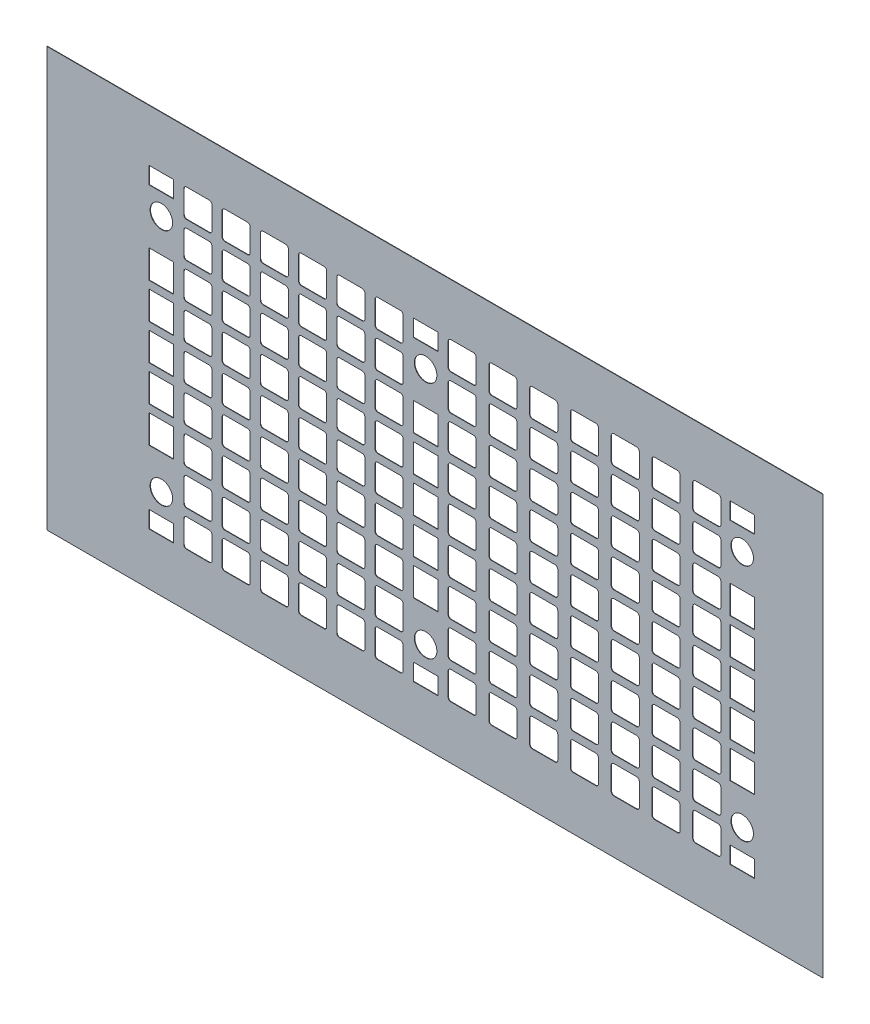
SolidWorks part; units mm, degrees
ref_plane "Спереди (XY)" through (0, 0, 0) normal (0, 0, 1) x (1, 0, 0)
ref_plane "Сверху (XZ)" through (0, 0, 0) normal (0, 1, 0) x (1, 0, 0)
ref_plane "Справа (ZY)" through (0, 0, 0) normal (1, 0, 0) x (0, 0, -1)
sketch "Эскиз1" plane through (0, 0, 0) normal (0, 0, 1) x (1, 0, 0)
  line L0 (-28, 59) -> (248, 59) construction
  line L1 (0, 0) -> (233, 0) construction
  line L2 (0, 0) -> (0, 118) construction
  line L3 (0, 118) -> (233, 118) construction
  line L4 (233, 0) -> (233, 118) construction
  line L5 (-28, -15.5) -> (248, -15.5)
  line L6 (-28, -15.5) -> (-28, 133.5)
  line L7 (-28, 133.5) -> (248, 133.5)
  line L8 (248, -15.5) -> (248, 133.5)
  line L9 (12.74, 16.55) -> (219.34, 16.55) construction
  line L10 (34.34, 114) -> (34.34, 106)
  line L11 (21.74, 115) -> (29.74, 115)
  line L12 (20.74, 114) -> (20.74, 106)
  line L13 (21.74, 105) -> (29.74, 105)
  line L14 (30.74, 114) -> (30.74, 106)
  line L15 (35.34, 115) -> (43.34, 115)
  line L16 (44.34, 114) -> (44.34, 106)
  line L17 (35.34, 105) -> (43.34, 105)
  line L18 (47.94, 114) -> (47.94, 106)
  line L19 (48.94, 115) -> (56.94, 115)
  line L20 (57.94, 114) -> (57.94, 106)
  line L21 (48.94, 105) -> (56.94, 105)
  line L22 (61.54, 114) -> (61.54, 106)
  line L23 (62.54, 115) -> (70.54, 115)
  line L24 (71.54, 114) -> (71.54, 106)
  line L25 (62.54, 105) -> (70.54, 105)
  line L26 (75.14, 114) -> (75.14, 106)
  line L27 (76.14, 115) -> (84.14, 115)
  line L28 (85.14, 114) -> (85.14, 106)
  line L29 (76.14, 105) -> (84.14, 105)
  line L30 (88.74, 114) -> (88.74, 106)
  line L31 (89.74, 115) -> (97.74, 115)
  line L32 (98.74, 114) -> (98.74, 106)
  line L33 (89.74, 105) -> (97.74, 105)
  line L34 (34.34, 101.3) -> (34.34, 93.3)
  line L35 (35.34, 102.3) -> (43.34, 102.3)
  line L36 (44.34, 101.3) -> (44.34, 93.3)
  line L37 (35.34, 92.3) -> (43.34, 92.3)
  line L38 (47.94, 101.3) -> (47.94, 93.3)
  line L39 (48.94, 102.3) -> (56.94, 102.3)
  line L40 (57.94, 101.3) -> (57.94, 93.3)
  line L41 (48.94, 92.3) -> (56.94, 92.3)
  line L42 (61.54, 101.3) -> (61.54, 93.3)
  line L43 (62.54, 102.3) -> (70.54, 102.3)
  line L44 (71.54, 101.3) -> (71.54, 93.3)
  line L45 (62.54, 92.3) -> (70.54, 92.3)
  line L46 (75.14, 101.3) -> (75.14, 93.3)
  line L47 (76.14, 102.3) -> (84.14, 102.3)
  line L48 (85.14, 101.3) -> (85.14, 93.3)
  line L49 (76.14, 92.3) -> (84.14, 92.3)
  line L50 (88.74, 101.3) -> (88.74, 93.3)
  line L51 (89.74, 102.3) -> (97.74, 102.3)
  line L52 (98.74, 101.3) -> (98.74, 93.3)
  line L53 (89.74, 92.3) -> (97.74, 92.3)
  line L54 (34.34, 88.6) -> (34.34, 80.6)
  line L55 (35.34, 89.6) -> (43.34, 89.6)
  line L56 (44.34, 88.6) -> (44.34, 80.6)
  line L57 (35.34, 79.6) -> (43.34, 79.6)
  line L58 (47.94, 88.6) -> (47.94, 80.6)
  line L59 (48.94, 89.6) -> (56.94, 89.6)
  line L60 (57.94, 88.6) -> (57.94, 80.6)
  line L61 (48.94, 79.6) -> (56.94, 79.6)
  line L62 (61.54, 88.6) -> (61.54, 80.6)
  line L63 (62.54, 89.6) -> (70.54, 89.6)
  line L64 (71.54, 88.6) -> (71.54, 80.6)
  line L65 (62.54, 79.6) -> (70.54, 79.6)
  line L66 (75.14, 88.6) -> (75.14, 80.6)
  line L67 (76.14, 89.6) -> (84.14, 89.6)
  line L68 (85.14, 88.6) -> (85.14, 80.6)
  line L69 (76.14, 79.6) -> (84.14, 79.6)
  line L70 (88.74, 88.6) -> (88.74, 80.6)
  line L71 (89.74, 89.6) -> (97.74, 89.6)
  line L72 (98.74, 88.6) -> (98.74, 80.6)
  line L73 (89.74, 79.6) -> (97.74, 79.6)
  line L74 (34.34, 75.9) -> (34.34, 67.9)
  line L75 (35.34, 76.9) -> (43.34, 76.9)
  line L76 (44.34, 75.9) -> (44.34, 67.9)
  line L77 (35.34, 66.9) -> (43.34, 66.9)
  line L78 (47.94, 75.9) -> (47.94, 67.9)
  line L79 (48.94, 76.9) -> (56.94, 76.9)
  line L80 (57.94, 75.9) -> (57.94, 67.9)
  line L81 (48.94, 66.9) -> (56.94, 66.9)
  line L82 (61.54, 75.9) -> (61.54, 67.9)
  line L83 (62.54, 76.9) -> (70.54, 76.9)
  line L84 (71.54, 75.9) -> (71.54, 67.9)
  line L85 (62.54, 66.9) -> (70.54, 66.9)
  line L86 (75.14, 75.9) -> (75.14, 67.9)
  line L87 (76.14, 76.9) -> (84.14, 76.9)
  line L88 (85.14, 75.9) -> (85.14, 67.9)
  line L89 (76.14, 66.9) -> (84.14, 66.9)
  line L90 (88.74, 75.9) -> (88.74, 67.9)
  line L91 (89.74, 76.9) -> (97.74, 76.9)
  line L92 (98.74, 75.9) -> (98.74, 67.9)
  line L93 (89.74, 66.9) -> (97.74, 66.9)
  line L94 (34.34, 63.2) -> (34.34, 55.2)
  line L95 (35.34, 64.2) -> (43.34, 64.2)
  line L96 (44.34, 63.2) -> (44.34, 55.2)
  line L97 (35.34, 54.2) -> (43.34, 54.2)
  line L98 (47.94, 63.2) -> (47.94, 55.2)
  line L99 (48.94, 64.2) -> (56.94, 64.2)
  line L100 (57.94, 63.2) -> (57.94, 55.2)
  line L101 (48.94, 54.2) -> (56.94, 54.2)
  line L102 (61.54, 63.2) -> (61.54, 55.2)
  line L103 (62.54, 64.2) -> (70.54, 64.2)
  line L104 (71.54, 63.2) -> (71.54, 55.2)
  line L105 (62.54, 54.2) -> (70.54, 54.2)
  line L106 (75.14, 63.2) -> (75.14, 55.2)
  line L107 (76.14, 64.2) -> (84.14, 64.2)
  line L108 (85.14, 63.2) -> (85.14, 55.2)
  line L109 (76.14, 54.2) -> (84.14, 54.2)
  line L110 (88.74, 63.2) -> (88.74, 55.2)
  line L111 (89.74, 64.2) -> (97.74, 64.2)
  line L112 (98.74, 63.2) -> (98.74, 55.2)
  line L113 (89.74, 54.2) -> (97.74, 54.2)
  line L114 (34.34, 50.5) -> (34.34, 42.5)
  line L115 (35.34, 51.5) -> (43.34, 51.5)
  line L116 (44.34, 50.5) -> (44.34, 42.5)
  line L117 (35.34, 41.5) -> (43.34, 41.5)
  line L118 (47.94, 50.5) -> (47.94, 42.5)
  line L119 (48.94, 51.5) -> (56.94, 51.5)
  line L120 (57.94, 50.5) -> (57.94, 42.5)
  line L121 (48.94, 41.5) -> (56.94, 41.5)
  line L122 (61.54, 50.5) -> (61.54, 42.5)
  line L123 (62.54, 51.5) -> (70.54, 51.5)
  line L124 (71.54, 50.5) -> (71.54, 42.5)
  line L125 (62.54, 41.5) -> (70.54, 41.5)
  line L126 (75.14, 50.5) -> (75.14, 42.5)
  line L127 (76.14, 51.5) -> (84.14, 51.5)
  line L128 (85.14, 50.5) -> (85.14, 42.5)
  line L129 (76.14, 41.5) -> (84.14, 41.5)
  line L130 (88.74, 50.5) -> (88.74, 42.5)
  line L131 (89.74, 51.5) -> (97.74, 51.5)
  line L132 (98.74, 50.5) -> (98.74, 42.5)
  line L133 (89.74, 41.5) -> (97.74, 41.5)
  line L134 (34.34, 37.8) -> (34.34, 29.8)
  line L135 (35.34, 38.8) -> (43.34, 38.8)
  line L136 (44.34, 37.8) -> (44.34, 29.8)
  line L137 (35.34, 28.8) -> (43.34, 28.8)
  line L138 (47.94, 37.8) -> (47.94, 29.8)
  line L139 (48.94, 38.8) -> (56.94, 38.8)
  line L140 (57.94, 37.8) -> (57.94, 29.8)
  line L141 (48.94, 28.8) -> (56.94, 28.8)
  line L142 (61.54, 37.8) -> (61.54, 29.8)
  line L143 (62.54, 38.8) -> (70.54, 38.8)
  line L144 (71.54, 37.8) -> (71.54, 29.8)
  line L145 (62.54, 28.8) -> (70.54, 28.8)
  line L146 (75.14, 37.8) -> (75.14, 29.8)
  line L147 (76.14, 38.8) -> (84.14, 38.8)
  line L148 (85.14, 37.8) -> (85.14, 29.8)
  line L149 (76.14, 28.8) -> (84.14, 28.8)
  line L150 (88.74, 37.8) -> (88.74, 29.8)
  line L151 (89.74, 38.8) -> (97.74, 38.8)
  line L152 (98.74, 37.8) -> (98.74, 29.8)
  line L153 (89.74, 28.8) -> (97.74, 28.8)
  line L154 (34.34, 25.1) -> (34.34, 17.1)
  line L155 (35.34, 26.1) -> (43.34, 26.1)
  line L156 (44.34, 25.1) -> (44.34, 17.1)
  line L157 (35.34, 16.1) -> (43.34, 16.1)
  line L158 (47.94, 25.1) -> (47.94, 17.1)
  line L159 (48.94, 26.1) -> (56.94, 26.1)
  line L160 (57.94, 25.1) -> (57.94, 17.1)
  line L161 (48.94, 16.1) -> (56.94, 16.1)
  line L162 (61.54, 25.1) -> (61.54, 17.1)
  line L163 (62.54, 26.1) -> (70.54, 26.1)
  line L164 (71.54, 25.1) -> (71.54, 17.1)
  line L165 (62.54, 16.1) -> (70.54, 16.1)
  line L166 (75.14, 25.1) -> (75.14, 17.1)
  line L167 (76.14, 26.1) -> (84.14, 26.1)
  line L168 (85.14, 25.1) -> (85.14, 17.1)
  line L169 (76.14, 16.1) -> (84.14, 16.1)
  line L170 (88.74, 25.1) -> (88.74, 17.1)
  line L171 (89.74, 26.1) -> (97.74, 26.1)
  line L172 (98.74, 25.1) -> (98.74, 17.1)
  line L173 (89.74, 16.1) -> (97.74, 16.1)
  line L174 (34.34, 12.4) -> (34.34, 4.4)
  line L175 (35.34, 13.4) -> (43.34, 13.4)
  line L176 (44.34, 12.4) -> (44.34, 4.4)
  line L177 (35.34, 3.4) -> (43.34, 3.4)
  line L178 (47.94, 12.4) -> (47.94, 4.4)
  line L179 (48.94, 13.4) -> (56.94, 13.4)
  line L180 (57.94, 12.4) -> (57.94, 4.4)
  line L181 (48.94, 3.4) -> (56.94, 3.4)
  line L182 (61.54, 12.4) -> (61.54, 4.4)
  line L183 (62.54, 13.4) -> (70.54, 13.4)
  line L184 (71.54, 12.4) -> (71.54, 4.4)
  line L185 (62.54, 3.4) -> (70.54, 3.4)
  line L186 (75.14, 12.4) -> (75.14, 4.4)
  line L187 (76.14, 13.4) -> (84.14, 13.4)
  line L188 (85.14, 12.4) -> (85.14, 4.4)
  line L189 (76.14, 3.4) -> (84.14, 3.4)
  line L190 (88.74, 12.4) -> (88.74, 4.4)
  line L191 (89.74, 13.4) -> (97.74, 13.4)
  line L192 (98.74, 12.4) -> (98.74, 4.4)
  line L193 (89.74, 3.4) -> (97.74, 3.4)
  line L194 (20.74, 101.3) -> (20.74, 93.3)
  line L195 (21.74, 102.3) -> (29.74, 102.3)
  line L196 (30.74, 101.3) -> (30.74, 93.3)
  line L197 (21.74, 92.3) -> (29.74, 92.3)
  line L198 (20.74, 88.6) -> (20.74, 80.6)
  line L199 (21.74, 89.6) -> (29.74, 89.6)
  line L200 (30.74, 88.6) -> (30.74, 80.6)
  line L201 (21.74, 79.6) -> (29.74, 79.6)
  line L202 (20.74, 75.9) -> (20.74, 67.9)
  line L203 (21.74, 76.9) -> (29.74, 76.9)
  line L204 (30.74, 75.9) -> (30.74, 67.9)
  line L205 (21.74, 66.9) -> (29.74, 66.9)
  line L206 (20.74, 63.2) -> (20.74, 55.2)
  line L207 (21.74, 64.2) -> (29.74, 64.2)
  line L208 (30.74, 63.2) -> (30.74, 55.2)
  line L209 (21.74, 54.2) -> (29.74, 54.2)
  line L210 (20.74, 50.5) -> (20.74, 42.5)
  line L211 (21.74, 51.5) -> (29.74, 51.5)
  line L212 (30.74, 50.5) -> (30.74, 42.5)
  line L213 (21.74, 41.5) -> (29.74, 41.5)
  line L214 (20.74, 37.8) -> (20.74, 29.8)
  line L215 (21.74, 38.8) -> (29.74, 38.8)
  line L216 (30.74, 37.8) -> (30.74, 29.8)
  line L217 (21.74, 28.8) -> (29.74, 28.8)
  line L218 (20.74, 25.1) -> (20.74, 17.1)
  line L219 (21.74, 26.1) -> (29.74, 26.1)
  line L220 (30.74, 25.1) -> (30.74, 17.1)
  line L221 (21.74, 16.1) -> (29.74, 16.1)
  line L222 (20.74, 12.4) -> (20.74, 4.4)
  line L223 (21.74, 13.4) -> (29.74, 13.4)
  line L224 (30.74, 12.4) -> (30.74, 4.4)
  line L225 (21.74, 3.4) -> (29.74, 3.4)
  line L226 (106.74, 16.55) -> (106.74, 101.45) construction
  line L227 (123.74, 115) -> (115.74, 115)
  line L228 (114.74, 114) -> (114.74, 106)
  line L229 (123.74, 105) -> (115.74, 105)
  line L230 (124.74, 114) -> (124.74, 106)
  line L231 (139.24, 114) -> (139.24, 106)
  line L232 (138.24, 105) -> (130.24, 105)
  line L233 (129.24, 114) -> (129.24, 106)
  line L234 (138.24, 115) -> (130.24, 115)
  line L235 (153.74, 114) -> (153.74, 106)
  line L236 (152.74, 105) -> (144.74, 105)
  line L237 (143.74, 114) -> (143.74, 106)
  line L238 (152.74, 115) -> (144.74, 115)
  line L239 (168.24, 114) -> (168.24, 106)
  line L240 (167.24, 105) -> (159.24, 105)
  line L241 (158.24, 114) -> (158.24, 106)
  line L242 (167.24, 115) -> (159.24, 115)
  line L243 (182.74, 114) -> (182.74, 106)
  line L244 (181.74, 105) -> (173.74, 105)
  line L245 (172.74, 114) -> (172.74, 106)
  line L246 (181.74, 115) -> (173.74, 115)
  line L247 (197.24, 114) -> (197.24, 106)
  line L248 (196.24, 105) -> (188.24, 105)
  line L249 (187.24, 114) -> (187.24, 106)
  line L250 (196.24, 115) -> (188.24, 115)
  line L251 (211.74, 114) -> (211.74, 106)
  line L252 (210.74, 105) -> (202.74, 105)
  line L253 (201.74, 114) -> (201.74, 106)
  line L254 (210.74, 115) -> (202.74, 115)
  line L255 (139.24, 101.3) -> (139.24, 93.3)
  line L256 (138.24, 92.3) -> (130.24, 92.3)
  line L257 (129.24, 101.3) -> (129.24, 93.3)
  line L258 (138.24, 102.3) -> (130.24, 102.3)
  line L259 (153.74, 101.3) -> (153.74, 93.3)
  line L260 (152.74, 92.3) -> (144.74, 92.3)
  line L261 (143.74, 101.3) -> (143.74, 93.3)
  line L262 (152.74, 102.3) -> (144.74, 102.3)
  line L263 (168.24, 101.3) -> (168.24, 93.3)
  line L264 (167.24, 92.3) -> (159.24, 92.3)
  line L265 (158.24, 101.3) -> (158.24, 93.3)
  line L266 (167.24, 102.3) -> (159.24, 102.3)
  line L267 (182.74, 101.3) -> (182.74, 93.3)
  line L268 (181.74, 92.3) -> (173.74, 92.3)
  line L269 (172.74, 101.3) -> (172.74, 93.3)
  line L270 (181.74, 102.3) -> (173.74, 102.3)
  line L271 (197.24, 101.3) -> (197.24, 93.3)
  line L272 (196.24, 92.3) -> (188.24, 92.3)
  line L273 (187.24, 101.3) -> (187.24, 93.3)
  line L274 (196.24, 102.3) -> (188.24, 102.3)
  line L275 (211.74, 101.3) -> (211.74, 93.3)
  line L276 (210.74, 92.3) -> (202.74, 92.3)
  line L277 (201.74, 101.3) -> (201.74, 93.3)
  line L278 (210.74, 102.3) -> (202.74, 102.3)
  line L279 (139.24, 88.6) -> (139.24, 80.6)
  line L280 (138.24, 79.6) -> (130.24, 79.6)
  line L281 (129.24, 88.6) -> (129.24, 80.6)
  line L282 (138.24, 89.6) -> (130.24, 89.6)
  line L283 (153.74, 88.6) -> (153.74, 80.6)
  line L284 (152.74, 79.6) -> (144.74, 79.6)
  line L285 (143.74, 88.6) -> (143.74, 80.6)
  line L286 (152.74, 89.6) -> (144.74, 89.6)
  line L287 (168.24, 88.6) -> (168.24, 80.6)
  line L288 (167.24, 79.6) -> (159.24, 79.6)
  line L289 (158.24, 88.6) -> (158.24, 80.6)
  line L290 (167.24, 89.6) -> (159.24, 89.6)
  line L291 (182.74, 88.6) -> (182.74, 80.6)
  line L292 (181.74, 79.6) -> (173.74, 79.6)
  line L293 (172.74, 88.6) -> (172.74, 80.6)
  line L294 (181.74, 89.6) -> (173.74, 89.6)
  line L295 (197.24, 88.6) -> (197.24, 80.6)
  line L296 (196.24, 79.6) -> (188.24, 79.6)
  line L297 (187.24, 88.6) -> (187.24, 80.6)
  line L298 (196.24, 89.6) -> (188.24, 89.6)
  line L299 (211.74, 88.6) -> (211.74, 80.6)
  line L300 (210.74, 79.6) -> (202.74, 79.6)
  line L301 (201.74, 88.6) -> (201.74, 80.6)
  line L302 (210.74, 89.6) -> (202.74, 89.6)
  line L303 (139.24, 75.9) -> (139.24, 67.9)
  line L304 (138.24, 66.9) -> (130.24, 66.9)
  line L305 (129.24, 75.9) -> (129.24, 67.9)
  line L306 (138.24, 76.9) -> (130.24, 76.9)
  line L307 (153.74, 75.9) -> (153.74, 67.9)
  line L308 (152.74, 66.9) -> (144.74, 66.9)
  line L309 (143.74, 75.9) -> (143.74, 67.9)
  line L310 (152.74, 76.9) -> (144.74, 76.9)
  line L311 (168.24, 75.9) -> (168.24, 67.9)
  line L312 (167.24, 66.9) -> (159.24, 66.9)
  line L313 (158.24, 75.9) -> (158.24, 67.9)
  line L314 (167.24, 76.9) -> (159.24, 76.9)
  line L315 (182.74, 75.9) -> (182.74, 67.9)
  line L316 (181.74, 66.9) -> (173.74, 66.9)
  line L317 (172.74, 75.9) -> (172.74, 67.9)
  line L318 (181.74, 76.9) -> (173.74, 76.9)
  line L319 (197.24, 75.9) -> (197.24, 67.9)
  line L320 (196.24, 66.9) -> (188.24, 66.9)
  line L321 (187.24, 75.9) -> (187.24, 67.9)
  line L322 (196.24, 76.9) -> (188.24, 76.9)
  line L323 (211.74, 75.9) -> (211.74, 67.9)
  line L324 (210.74, 66.9) -> (202.74, 66.9)
  line L325 (201.74, 75.9) -> (201.74, 67.9)
  line L326 (210.74, 76.9) -> (202.74, 76.9)
  line L327 (139.24, 63.2) -> (139.24, 55.2)
  line L328 (138.24, 54.2) -> (130.24, 54.2)
  line L329 (129.24, 63.2) -> (129.24, 55.2)
  line L330 (138.24, 64.2) -> (130.24, 64.2)
  line L331 (153.74, 63.2) -> (153.74, 55.2)
  line L332 (152.74, 54.2) -> (144.74, 54.2)
  line L333 (143.74, 63.2) -> (143.74, 55.2)
  line L334 (152.74, 64.2) -> (144.74, 64.2)
  line L335 (168.24, 63.2) -> (168.24, 55.2)
  line L336 (167.24, 54.2) -> (159.24, 54.2)
  line L337 (158.24, 63.2) -> (158.24, 55.2)
  line L338 (167.24, 64.2) -> (159.24, 64.2)
  line L339 (182.74, 63.2) -> (182.74, 55.2)
  line L340 (181.74, 54.2) -> (173.74, 54.2)
  line L341 (172.74, 63.2) -> (172.74, 55.2)
  line L342 (181.74, 64.2) -> (173.74, 64.2)
  line L343 (197.24, 63.2) -> (197.24, 55.2)
  line L344 (196.24, 54.2) -> (188.24, 54.2)
  line L345 (187.24, 63.2) -> (187.24, 55.2)
  line L346 (196.24, 64.2) -> (188.24, 64.2)
  line L347 (211.74, 63.2) -> (211.74, 55.2)
  line L348 (210.74, 54.2) -> (202.74, 54.2)
  line L349 (201.74, 63.2) -> (201.74, 55.2)
  line L350 (210.74, 64.2) -> (202.74, 64.2)
  line L351 (139.24, 50.5) -> (139.24, 42.5)
  line L352 (138.24, 41.5) -> (130.24, 41.5)
  line L353 (129.24, 50.5) -> (129.24, 42.5)
  line L354 (138.24, 51.5) -> (130.24, 51.5)
  line L355 (153.74, 50.5) -> (153.74, 42.5)
  line L356 (152.74, 41.5) -> (144.74, 41.5)
  line L357 (143.74, 50.5) -> (143.74, 42.5)
  line L358 (152.74, 51.5) -> (144.74, 51.5)
  line L359 (168.24, 50.5) -> (168.24, 42.5)
  line L360 (167.24, 41.5) -> (159.24, 41.5)
  line L361 (158.24, 50.5) -> (158.24, 42.5)
  line L362 (167.24, 51.5) -> (159.24, 51.5)
  line L363 (182.74, 50.5) -> (182.74, 42.5)
  line L364 (181.74, 41.5) -> (173.74, 41.5)
  line L365 (172.74, 50.5) -> (172.74, 42.5)
  line L366 (181.74, 51.5) -> (173.74, 51.5)
  line L367 (197.24, 50.5) -> (197.24, 42.5)
  line L368 (196.24, 41.5) -> (188.24, 41.5)
  line L369 (187.24, 50.5) -> (187.24, 42.5)
  line L370 (196.24, 51.5) -> (188.24, 51.5)
  line L371 (211.74, 50.5) -> (211.74, 42.5)
  line L372 (210.74, 41.5) -> (202.74, 41.5)
  line L373 (201.74, 50.5) -> (201.74, 42.5)
  line L374 (210.74, 51.5) -> (202.74, 51.5)
  line L375 (139.24, 37.8) -> (139.24, 29.8)
  line L376 (138.24, 28.8) -> (130.24, 28.8)
  line L377 (129.24, 37.8) -> (129.24, 29.8)
  line L378 (138.24, 38.8) -> (130.24, 38.8)
  line L379 (153.74, 37.8) -> (153.74, 29.8)
  line L380 (152.74, 28.8) -> (144.74, 28.8)
  line L381 (143.74, 37.8) -> (143.74, 29.8)
  line L382 (152.74, 38.8) -> (144.74, 38.8)
  line L383 (168.24, 37.8) -> (168.24, 29.8)
  line L384 (167.24, 28.8) -> (159.24, 28.8)
  line L385 (158.24, 37.8) -> (158.24, 29.8)
  line L386 (167.24, 38.8) -> (159.24, 38.8)
  line L387 (182.74, 37.8) -> (182.74, 29.8)
  line L388 (181.74, 28.8) -> (173.74, 28.8)
  line L389 (172.74, 37.8) -> (172.74, 29.8)
  line L390 (181.74, 38.8) -> (173.74, 38.8)
  line L391 (197.24, 37.8) -> (197.24, 29.8)
  line L392 (196.24, 28.8) -> (188.24, 28.8)
  line L393 (187.24, 37.8) -> (187.24, 29.8)
  line L394 (196.24, 38.8) -> (188.24, 38.8)
  line L395 (211.74, 37.8) -> (211.74, 29.8)
  line L396 (210.74, 28.8) -> (202.74, 28.8)
  line L397 (201.74, 37.8) -> (201.74, 29.8)
  line L398 (210.74, 38.8) -> (202.74, 38.8)
  line L399 (139.24, 25.1) -> (139.24, 17.1)
  line L400 (138.24, 16.1) -> (130.24, 16.1)
  line L401 (129.24, 25.1) -> (129.24, 17.1)
  line L402 (138.24, 26.1) -> (130.24, 26.1)
  line L403 (153.74, 25.1) -> (153.74, 17.1)
  line L404 (152.74, 16.1) -> (144.74, 16.1)
  line L405 (143.74, 25.1) -> (143.74, 17.1)
  line L406 (152.74, 26.1) -> (144.74, 26.1)
  line L407 (168.24, 25.1) -> (168.24, 17.1)
  line L408 (167.24, 16.1) -> (159.24, 16.1)
  line L409 (158.24, 25.1) -> (158.24, 17.1)
  line L410 (167.24, 26.1) -> (159.24, 26.1)
  line L411 (182.74, 25.1) -> (182.74, 17.1)
  line L412 (181.74, 16.1) -> (173.74, 16.1)
  line L413 (172.74, 25.1) -> (172.74, 17.1)
  line L414 (181.74, 26.1) -> (173.74, 26.1)
  line L415 (197.24, 25.1) -> (197.24, 17.1)
  line L416 (196.24, 16.1) -> (188.24, 16.1)
  line L417 (187.24, 25.1) -> (187.24, 17.1)
  line L418 (196.24, 26.1) -> (188.24, 26.1)
  line L419 (211.74, 25.1) -> (211.74, 17.1)
  line L420 (210.74, 16.1) -> (202.74, 16.1)
  line L421 (201.74, 25.1) -> (201.74, 17.1)
  line L422 (210.74, 26.1) -> (202.74, 26.1)
  line L423 (139.24, 12.4) -> (139.24, 4.4)
  line L424 (138.24, 3.4) -> (130.24, 3.4)
  line L425 (129.24, 12.4) -> (129.24, 4.4)
  line L426 (138.24, 13.4) -> (130.24, 13.4)
  line L427 (153.74, 12.4) -> (153.74, 4.4)
  line L428 (152.74, 3.4) -> (144.74, 3.4)
  line L429 (143.74, 12.4) -> (143.74, 4.4)
  line L430 (152.74, 13.4) -> (144.74, 13.4)
  line L431 (168.24, 12.4) -> (168.24, 4.4)
  line L432 (167.24, 3.4) -> (159.24, 3.4)
  line L433 (158.24, 12.4) -> (158.24, 4.4)
  line L434 (167.24, 13.4) -> (159.24, 13.4)
  line L435 (182.74, 12.4) -> (182.74, 4.4)
  line L436 (181.74, 3.4) -> (173.74, 3.4)
  line L437 (172.74, 12.4) -> (172.74, 4.4)
  line L438 (181.74, 13.4) -> (173.74, 13.4)
  line L439 (197.24, 12.4) -> (197.24, 4.4)
  line L440 (196.24, 3.4) -> (188.24, 3.4)
  line L441 (187.24, 12.4) -> (187.24, 4.4)
  line L442 (196.24, 13.4) -> (188.24, 13.4)
  line L443 (211.74, 12.4) -> (211.74, 4.4)
  line L444 (210.74, 3.4) -> (202.74, 3.4)
  line L445 (201.74, 12.4) -> (201.74, 4.4)
  line L446 (210.74, 13.4) -> (202.74, 13.4)
  line L447 (124.74, 101.3) -> (124.74, 93.3)
  line L448 (123.74, 92.3) -> (115.74, 92.3)
  line L449 (114.74, 101.3) -> (114.74, 93.3)
  line L450 (123.74, 102.3) -> (115.74, 102.3)
  line L451 (124.74, 88.6) -> (124.74, 80.6)
  line L452 (123.74, 79.6) -> (115.74, 79.6)
  line L453 (114.74, 88.6) -> (114.74, 80.6)
  line L454 (123.74, 89.6) -> (115.74, 89.6)
  line L455 (124.74, 75.9) -> (124.74, 67.9)
  line L456 (123.74, 66.9) -> (115.74, 66.9)
  line L457 (114.74, 75.9) -> (114.74, 67.9)
  line L458 (123.74, 76.9) -> (115.74, 76.9)
  line L459 (124.74, 63.2) -> (124.74, 55.2)
  line L460 (123.74, 54.2) -> (115.74, 54.2)
  line L461 (114.74, 63.2) -> (114.74, 55.2)
  line L462 (123.74, 64.2) -> (115.74, 64.2)
  line L463 (124.74, 50.5) -> (124.74, 42.5)
  line L464 (123.74, 41.5) -> (115.74, 41.5)
  line L465 (114.74, 50.5) -> (114.74, 42.5)
  line L466 (123.74, 51.5) -> (115.74, 51.5)
  line L467 (124.74, 37.8) -> (124.74, 29.8)
  line L468 (123.74, 28.8) -> (115.74, 28.8)
  line L469 (114.74, 37.8) -> (114.74, 29.8)
  line L470 (123.74, 38.8) -> (115.74, 38.8)
  line L471 (124.74, 25.1) -> (124.74, 17.1)
  line L472 (123.74, 16.1) -> (115.74, 16.1)
  line L473 (114.74, 25.1) -> (114.74, 17.1)
  line L474 (123.74, 26.1) -> (115.74, 26.1)
  line L475 (124.74, 12.4) -> (124.74, 4.4)
  line L476 (123.74, 3.4) -> (115.74, 3.4)
  line L477 (114.74, 12.4) -> (114.74, 4.4)
  line L478 (123.74, 13.4) -> (115.74, 13.4)
  line L483 (102.34, 76.9) -> (102.34, 66.9)
  line L484 (102.34, 89.6) -> (111.14, 89.6)
  line L485 (102.34, 89.6) -> (102.34, 79.6)
  line L486 (102.34, 79.6) -> (111.14, 79.6)
  line L487 (111.14, 89.6) -> (111.14, 79.6)
  line L488 (102.34, 76.9) -> (111.14, 76.9)
  line L489 (111.14, 76.9) -> (111.14, 66.9)
  line L490 (102.34, 66.9) -> (111.14, 66.9)
  line L491 (102.34, 64.2) -> (102.34, 54.2)
  line L492 (102.34, 64.2) -> (111.14, 64.2)
  line L493 (111.14, 64.2) -> (111.14, 54.2)
  line L494 (102.34, 54.2) -> (111.14, 54.2)
  line L495 (102.34, 51.5) -> (102.34, 41.5)
  line L496 (102.34, 51.5) -> (111.14, 51.5)
  line L497 (111.14, 51.5) -> (111.14, 41.5)
  line L498 (102.34, 41.5) -> (111.14, 41.5)
  line L499 (102.34, 38.8) -> (102.34, 28.8)
  line L500 (102.34, 38.8) -> (111.14, 38.8)
  line L501 (111.14, 38.8) -> (111.14, 28.8)
  line L502 (102.34, 28.8) -> (111.14, 28.8)
  line L503 (106.74, 101.45) -> (219.34, 101.45) construction
  line L504 (106.74, 101.45) -> (12.74, 101.45) construction
  line L505 (163.04, 101.45) -> (163.04, 0) construction
  line L506 (59.74, 101.45) -> (59.74, 0) construction
  line L507 (102.34, 9) -> (111.14, 9)
  line L508 (102.34, 115) -> (111.14, 115)
  line L509 (102.34, 115) -> (102.34, 109)
  line L510 (102.34, 109) -> (111.14, 109)
  line L511 (111.14, 115) -> (111.14, 109)
  line L512 (111.14, 3) -> (111.14, 9)
  line L513 (102.34, 3) -> (111.14, 3)
  line L514 (102.34, 3) -> (102.34, 9)
  line L515 (223.74, 3) -> (223.74, 9)
  line L516 (223.74, 3) -> (214.94, 3)
  line L517 (214.94, 3) -> (214.94, 9)
  line L518 (223.74, 9) -> (214.94, 9)
  line L519 (223.74, 38.8) -> (214.94, 38.8)
  line L520 (223.74, 51.5) -> (214.94, 51.5)
  line L521 (214.94, 51.5) -> (214.94, 41.5)
  line L522 (223.74, 41.5) -> (214.94, 41.5)
  line L523 (223.74, 51.5) -> (223.74, 41.5)
  line L524 (223.74, 64.2) -> (214.94, 64.2)
  line L525 (214.94, 64.2) -> (214.94, 54.2)
  line L526 (223.74, 54.2) -> (214.94, 54.2)
  line L527 (223.74, 64.2) -> (223.74, 54.2)
  line L528 (223.74, 76.9) -> (214.94, 76.9)
  line L529 (214.94, 76.9) -> (214.94, 66.9)
  line L530 (223.74, 66.9) -> (214.94, 66.9)
  line L531 (223.74, 76.9) -> (223.74, 66.9)
  line L532 (223.74, 79.6) -> (214.94, 79.6)
  line L533 (214.94, 89.6) -> (214.94, 79.6)
  line L534 (223.74, 89.6) -> (214.94, 89.6)
  line L535 (223.74, 89.6) -> (223.74, 79.6)
  line L536 (223.74, 109) -> (214.94, 109)
  line L537 (214.94, 115) -> (214.94, 109)
  line L538 (223.74, 115) -> (214.94, 115)
  line L539 (223.74, 115) -> (223.74, 109)
  line L540 (17.14, 51.5) -> (8.34, 51.5)
  line L541 (8.34, 51.5) -> (8.34, 41.5)
  line L542 (17.14, 41.5) -> (8.34, 41.5)
  line L543 (17.14, 51.5) -> (17.14, 41.5)
  line L544 (17.14, 3) -> (17.14, 9)
  line L545 (17.14, 3) -> (8.34, 3)
  line L546 (8.34, 3) -> (8.34, 9)
  line L547 (17.14, 9) -> (8.34, 9)
  line L548 (17.14, 38.8) -> (8.34, 38.8)
  line L549 (8.34, 38.8) -> (8.34, 28.8)
  line L550 (17.14, 28.8) -> (8.34, 28.8)
  line L551 (17.14, 38.8) -> (17.14, 28.8)
  line L552 (17.14, 64.2) -> (8.34, 64.2)
  line L553 (8.34, 64.2) -> (8.34, 54.2)
  line L554 (17.14, 54.2) -> (8.34, 54.2)
  line L555 (17.14, 64.2) -> (17.14, 54.2)
  line L556 (17.14, 76.9) -> (8.34, 76.9)
  line L557 (8.34, 76.9) -> (8.34, 66.9)
  line L558 (17.14, 66.9) -> (8.34, 66.9)
  line L559 (17.14, 76.9) -> (17.14, 66.9)
  line L560 (17.14, 79.6) -> (8.34, 79.6)
  line L561 (8.34, 89.6) -> (8.34, 79.6)
  line L562 (17.14, 89.6) -> (8.34, 89.6)
  line L563 (17.14, 89.6) -> (17.14, 79.6)
  line L564 (17.14, 109) -> (8.34, 109)
  line L565 (8.34, 115) -> (8.34, 109)
  line L566 (17.14, 115) -> (8.34, 115)
  line L567 (17.14, 115) -> (17.14, 109)
  line L568 (214.94, 38.8) -> (214.94, 28.8)
  line L569 (223.74, 28.8) -> (214.94, 28.8)
  line L570 (223.74, 38.8) -> (223.74, 28.8)
  circle A0 centre (12.74, 16.55) radius 4
  circle A1 centre (106.74, 16.55) radius 4
  circle A2 centre (219.34, 16.55) radius 4
  circle A3 centre (12.74, 101.45) radius 4
  circle A4 centre (106.74, 101.45) radius 4
  circle A5 centre (219.34, 101.45) radius 4
  arc A6 (21.74, 115) -> (20.74, 114) centre (21.74, 114) ccw
  arc A7 (20.74, 106) -> (21.74, 105) centre (21.74, 106) ccw
  arc A8 (29.74, 105) -> (30.74, 106) centre (29.74, 106) ccw
  arc A9 (29.74, 115) -> (30.74, 114) centre (29.74, 114) cw
  arc A10 (34.34, 106) -> (35.34, 105) centre (35.34, 106) ccw
  arc A11 (35.34, 115) -> (34.34, 114) centre (35.34, 114) ccw
  arc A12 (43.34, 115) -> (44.34, 114) centre (43.34, 114) cw
  arc A13 (43.34, 105) -> (44.34, 106) centre (43.34, 106) ccw
  arc A14 (47.94, 106) -> (48.94, 105) centre (48.94, 106) ccw
  arc A15 (48.94, 115) -> (47.94, 114) centre (48.94, 114) ccw
  arc A16 (56.94, 115) -> (57.94, 114) centre (56.94, 114) cw
  arc A17 (56.94, 105) -> (57.94, 106) centre (56.94, 106) ccw
  arc A18 (61.54, 106) -> (62.54, 105) centre (62.54, 106) ccw
  arc A19 (62.54, 115) -> (61.54, 114) centre (62.54, 114) ccw
  arc A20 (70.54, 115) -> (71.54, 114) centre (70.54, 114) cw
  arc A21 (70.54, 105) -> (71.54, 106) centre (70.54, 106) ccw
  arc A22 (75.14, 106) -> (76.14, 105) centre (76.14, 106) ccw
  arc A23 (76.14, 115) -> (75.14, 114) centre (76.14, 114) ccw
  arc A24 (84.14, 115) -> (85.14, 114) centre (84.14, 114) cw
  arc A25 (84.14, 105) -> (85.14, 106) centre (84.14, 106) ccw
  arc A26 (88.74, 106) -> (89.74, 105) centre (89.74, 106) ccw
  arc A27 (89.74, 115) -> (88.74, 114) centre (89.74, 114) ccw
  arc A28 (97.74, 115) -> (98.74, 114) centre (97.74, 114) cw
  arc A29 (97.74, 105) -> (98.74, 106) centre (97.74, 106) ccw
  arc A30 (34.34, 93.3) -> (35.34, 92.3) centre (35.34, 93.3) ccw
  arc A31 (35.34, 102.3) -> (34.34, 101.3) centre (35.34, 101.3) ccw
  arc A32 (43.34, 102.3) -> (44.34, 101.3) centre (43.34, 101.3) cw
  arc A33 (43.34, 92.3) -> (44.34, 93.3) centre (43.34, 93.3) ccw
  arc A34 (47.94, 93.3) -> (48.94, 92.3) centre (48.94, 93.3) ccw
  arc A35 (48.94, 102.3) -> (47.94, 101.3) centre (48.94, 101.3) ccw
  arc A36 (56.94, 102.3) -> (57.94, 101.3) centre (56.94, 101.3) cw
  arc A37 (56.94, 92.3) -> (57.94, 93.3) centre (56.94, 93.3) ccw
  arc A38 (61.54, 93.3) -> (62.54, 92.3) centre (62.54, 93.3) ccw
  arc A39 (62.54, 102.3) -> (61.54, 101.3) centre (62.54, 101.3) ccw
  arc A40 (70.54, 102.3) -> (71.54, 101.3) centre (70.54, 101.3) cw
  arc A41 (70.54, 92.3) -> (71.54, 93.3) centre (70.54, 93.3) ccw
  arc A42 (75.14, 93.3) -> (76.14, 92.3) centre (76.14, 93.3) ccw
  arc A43 (76.14, 102.3) -> (75.14, 101.3) centre (76.14, 101.3) ccw
  arc A44 (84.14, 102.3) -> (85.14, 101.3) centre (84.14, 101.3) cw
  arc A45 (84.14, 92.3) -> (85.14, 93.3) centre (84.14, 93.3) ccw
  arc A46 (88.74, 93.3) -> (89.74, 92.3) centre (89.74, 93.3) ccw
  arc A47 (89.74, 102.3) -> (88.74, 101.3) centre (89.74, 101.3) ccw
  arc A48 (97.74, 102.3) -> (98.74, 101.3) centre (97.74, 101.3) cw
  arc A49 (97.74, 92.3) -> (98.74, 93.3) centre (97.74, 93.3) ccw
  arc A50 (34.34, 80.6) -> (35.34, 79.6) centre (35.34, 80.6) ccw
  arc A51 (35.34, 89.6) -> (34.34, 88.6) centre (35.34, 88.6) ccw
  arc A52 (43.34, 89.6) -> (44.34, 88.6) centre (43.34, 88.6) cw
  arc A53 (43.34, 79.6) -> (44.34, 80.6) centre (43.34, 80.6) ccw
  arc A54 (47.94, 80.6) -> (48.94, 79.6) centre (48.94, 80.6) ccw
  arc A55 (48.94, 89.6) -> (47.94, 88.6) centre (48.94, 88.6) ccw
  arc A56 (56.94, 89.6) -> (57.94, 88.6) centre (56.94, 88.6) cw
  arc A57 (56.94, 79.6) -> (57.94, 80.6) centre (56.94, 80.6) ccw
  arc A58 (61.54, 80.6) -> (62.54, 79.6) centre (62.54, 80.6) ccw
  arc A59 (62.54, 89.6) -> (61.54, 88.6) centre (62.54, 88.6) ccw
  arc A60 (70.54, 89.6) -> (71.54, 88.6) centre (70.54, 88.6) cw
  arc A61 (70.54, 79.6) -> (71.54, 80.6) centre (70.54, 80.6) ccw
  arc A62 (75.14, 80.6) -> (76.14, 79.6) centre (76.14, 80.6) ccw
  arc A63 (76.14, 89.6) -> (75.14, 88.6) centre (76.14, 88.6) ccw
  arc A64 (84.14, 89.6) -> (85.14, 88.6) centre (84.14, 88.6) cw
  arc A65 (84.14, 79.6) -> (85.14, 80.6) centre (84.14, 80.6) ccw
  arc A66 (88.74, 80.6) -> (89.74, 79.6) centre (89.74, 80.6) ccw
  arc A67 (89.74, 89.6) -> (88.74, 88.6) centre (89.74, 88.6) ccw
  arc A68 (97.74, 89.6) -> (98.74, 88.6) centre (97.74, 88.6) cw
  arc A69 (97.74, 79.6) -> (98.74, 80.6) centre (97.74, 80.6) ccw
  arc A70 (34.34, 67.9) -> (35.34, 66.9) centre (35.34, 67.9) ccw
  arc A71 (35.34, 76.9) -> (34.34, 75.9) centre (35.34, 75.9) ccw
  arc A72 (43.34, 76.9) -> (44.34, 75.9) centre (43.34, 75.9) cw
  arc A73 (43.34, 66.9) -> (44.34, 67.9) centre (43.34, 67.9) ccw
  arc A74 (47.94, 67.9) -> (48.94, 66.9) centre (48.94, 67.9) ccw
  arc A75 (48.94, 76.9) -> (47.94, 75.9) centre (48.94, 75.9) ccw
  arc A76 (56.94, 76.9) -> (57.94, 75.9) centre (56.94, 75.9) cw
  arc A77 (56.94, 66.9) -> (57.94, 67.9) centre (56.94, 67.9) ccw
  arc A78 (61.54, 67.9) -> (62.54, 66.9) centre (62.54, 67.9) ccw
  arc A79 (62.54, 76.9) -> (61.54, 75.9) centre (62.54, 75.9) ccw
  arc A80 (70.54, 76.9) -> (71.54, 75.9) centre (70.54, 75.9) cw
  arc A81 (70.54, 66.9) -> (71.54, 67.9) centre (70.54, 67.9) ccw
  arc A82 (75.14, 67.9) -> (76.14, 66.9) centre (76.14, 67.9) ccw
  arc A83 (76.14, 76.9) -> (75.14, 75.9) centre (76.14, 75.9) ccw
  arc A84 (84.14, 76.9) -> (85.14, 75.9) centre (84.14, 75.9) cw
  arc A85 (84.14, 66.9) -> (85.14, 67.9) centre (84.14, 67.9) ccw
  arc A86 (88.74, 67.9) -> (89.74, 66.9) centre (89.74, 67.9) ccw
  arc A87 (89.74, 76.9) -> (88.74, 75.9) centre (89.74, 75.9) ccw
  arc A88 (97.74, 76.9) -> (98.74, 75.9) centre (97.74, 75.9) cw
  arc A89 (97.74, 66.9) -> (98.74, 67.9) centre (97.74, 67.9) ccw
  arc A90 (34.34, 55.2) -> (35.34, 54.2) centre (35.34, 55.2) ccw
  arc A91 (35.34, 64.2) -> (34.34, 63.2) centre (35.34, 63.2) ccw
  arc A92 (43.34, 64.2) -> (44.34, 63.2) centre (43.34, 63.2) cw
  arc A93 (43.34, 54.2) -> (44.34, 55.2) centre (43.34, 55.2) ccw
  arc A94 (47.94, 55.2) -> (48.94, 54.2) centre (48.94, 55.2) ccw
  arc A95 (48.94, 64.2) -> (47.94, 63.2) centre (48.94, 63.2) ccw
  arc A96 (56.94, 64.2) -> (57.94, 63.2) centre (56.94, 63.2) cw
  arc A97 (56.94, 54.2) -> (57.94, 55.2) centre (56.94, 55.2) ccw
  arc A98 (61.54, 55.2) -> (62.54, 54.2) centre (62.54, 55.2) ccw
  arc A99 (62.54, 64.2) -> (61.54, 63.2) centre (62.54, 63.2) ccw
  arc A100 (70.54, 64.2) -> (71.54, 63.2) centre (70.54, 63.2) cw
  arc A101 (70.54, 54.2) -> (71.54, 55.2) centre (70.54, 55.2) ccw
  arc A102 (75.14, 55.2) -> (76.14, 54.2) centre (76.14, 55.2) ccw
  arc A103 (76.14, 64.2) -> (75.14, 63.2) centre (76.14, 63.2) ccw
  arc A104 (84.14, 64.2) -> (85.14, 63.2) centre (84.14, 63.2) cw
  arc A105 (84.14, 54.2) -> (85.14, 55.2) centre (84.14, 55.2) ccw
  arc A106 (88.74, 55.2) -> (89.74, 54.2) centre (89.74, 55.2) ccw
  arc A107 (89.74, 64.2) -> (88.74, 63.2) centre (89.74, 63.2) ccw
  arc A108 (97.74, 64.2) -> (98.74, 63.2) centre (97.74, 63.2) cw
  arc A109 (97.74, 54.2) -> (98.74, 55.2) centre (97.74, 55.2) ccw
  arc A110 (34.34, 42.5) -> (35.34, 41.5) centre (35.34, 42.5) ccw
  arc A111 (35.34, 51.5) -> (34.34, 50.5) centre (35.34, 50.5) ccw
  arc A112 (43.34, 51.5) -> (44.34, 50.5) centre (43.34, 50.5) cw
  arc A113 (43.34, 41.5) -> (44.34, 42.5) centre (43.34, 42.5) ccw
  arc A114 (47.94, 42.5) -> (48.94, 41.5) centre (48.94, 42.5) ccw
  arc A115 (48.94, 51.5) -> (47.94, 50.5) centre (48.94, 50.5) ccw
  arc A116 (56.94, 51.5) -> (57.94, 50.5) centre (56.94, 50.5) cw
  arc A117 (56.94, 41.5) -> (57.94, 42.5) centre (56.94, 42.5) ccw
  arc A118 (61.54, 42.5) -> (62.54, 41.5) centre (62.54, 42.5) ccw
  arc A119 (62.54, 51.5) -> (61.54, 50.5) centre (62.54, 50.5) ccw
  arc A120 (70.54, 51.5) -> (71.54, 50.5) centre (70.54, 50.5) cw
  arc A121 (70.54, 41.5) -> (71.54, 42.5) centre (70.54, 42.5) ccw
  arc A122 (75.14, 42.5) -> (76.14, 41.5) centre (76.14, 42.5) ccw
  arc A123 (76.14, 51.5) -> (75.14, 50.5) centre (76.14, 50.5) ccw
  arc A124 (84.14, 51.5) -> (85.14, 50.5) centre (84.14, 50.5) cw
  arc A125 (84.14, 41.5) -> (85.14, 42.5) centre (84.14, 42.5) ccw
  arc A126 (88.74, 42.5) -> (89.74, 41.5) centre (89.74, 42.5) ccw
  arc A127 (89.74, 51.5) -> (88.74, 50.5) centre (89.74, 50.5) ccw
  arc A128 (97.74, 51.5) -> (98.74, 50.5) centre (97.74, 50.5) cw
  arc A129 (97.74, 41.5) -> (98.74, 42.5) centre (97.74, 42.5) ccw
  arc A130 (34.34, 29.8) -> (35.34, 28.8) centre (35.34, 29.8) ccw
  arc A131 (35.34, 38.8) -> (34.34, 37.8) centre (35.34, 37.8) ccw
  arc A132 (43.34, 38.8) -> (44.34, 37.8) centre (43.34, 37.8) cw
  arc A133 (43.34, 28.8) -> (44.34, 29.8) centre (43.34, 29.8) ccw
  arc A134 (47.94, 29.8) -> (48.94, 28.8) centre (48.94, 29.8) ccw
  arc A135 (48.94, 38.8) -> (47.94, 37.8) centre (48.94, 37.8) ccw
  arc A136 (56.94, 38.8) -> (57.94, 37.8) centre (56.94, 37.8) cw
  arc A137 (56.94, 28.8) -> (57.94, 29.8) centre (56.94, 29.8) ccw
  arc A138 (61.54, 29.8) -> (62.54, 28.8) centre (62.54, 29.8) ccw
  arc A139 (62.54, 38.8) -> (61.54, 37.8) centre (62.54, 37.8) ccw
  arc A140 (70.54, 38.8) -> (71.54, 37.8) centre (70.54, 37.8) cw
  arc A141 (70.54, 28.8) -> (71.54, 29.8) centre (70.54, 29.8) ccw
  arc A142 (75.14, 29.8) -> (76.14, 28.8) centre (76.14, 29.8) ccw
  arc A143 (76.14, 38.8) -> (75.14, 37.8) centre (76.14, 37.8) ccw
  arc A144 (84.14, 38.8) -> (85.14, 37.8) centre (84.14, 37.8) cw
  arc A145 (84.14, 28.8) -> (85.14, 29.8) centre (84.14, 29.8) ccw
  arc A146 (88.74, 29.8) -> (89.74, 28.8) centre (89.74, 29.8) ccw
  arc A147 (89.74, 38.8) -> (88.74, 37.8) centre (89.74, 37.8) ccw
  arc A148 (97.74, 38.8) -> (98.74, 37.8) centre (97.74, 37.8) cw
  arc A149 (97.74, 28.8) -> (98.74, 29.8) centre (97.74, 29.8) ccw
  arc A150 (34.34, 17.1) -> (35.34, 16.1) centre (35.34, 17.1) ccw
  arc A151 (35.34, 26.1) -> (34.34, 25.1) centre (35.34, 25.1) ccw
  arc A152 (43.34, 26.1) -> (44.34, 25.1) centre (43.34, 25.1) cw
  arc A153 (43.34, 16.1) -> (44.34, 17.1) centre (43.34, 17.1) ccw
  arc A154 (47.94, 17.1) -> (48.94, 16.1) centre (48.94, 17.1) ccw
  arc A155 (48.94, 26.1) -> (47.94, 25.1) centre (48.94, 25.1) ccw
  arc A156 (56.94, 26.1) -> (57.94, 25.1) centre (56.94, 25.1) cw
  arc A157 (56.94, 16.1) -> (57.94, 17.1) centre (56.94, 17.1) ccw
  arc A158 (61.54, 17.1) -> (62.54, 16.1) centre (62.54, 17.1) ccw
  arc A159 (62.54, 26.1) -> (61.54, 25.1) centre (62.54, 25.1) ccw
  arc A160 (70.54, 26.1) -> (71.54, 25.1) centre (70.54, 25.1) cw
  arc A161 (70.54, 16.1) -> (71.54, 17.1) centre (70.54, 17.1) ccw
  arc A162 (75.14, 17.1) -> (76.14, 16.1) centre (76.14, 17.1) ccw
  arc A163 (76.14, 26.1) -> (75.14, 25.1) centre (76.14, 25.1) ccw
  arc A164 (84.14, 26.1) -> (85.14, 25.1) centre (84.14, 25.1) cw
  arc A165 (84.14, 16.1) -> (85.14, 17.1) centre (84.14, 17.1) ccw
  arc A166 (88.74, 17.1) -> (89.74, 16.1) centre (89.74, 17.1) ccw
  arc A167 (89.74, 26.1) -> (88.74, 25.1) centre (89.74, 25.1) ccw
  arc A168 (97.74, 26.1) -> (98.74, 25.1) centre (97.74, 25.1) cw
  arc A169 (97.74, 16.1) -> (98.74, 17.1) centre (97.74, 17.1) ccw
  arc A170 (34.34, 4.4) -> (35.34, 3.4) centre (35.34, 4.4) ccw
  arc A171 (35.34, 13.4) -> (34.34, 12.4) centre (35.34, 12.4) ccw
  arc A172 (43.34, 13.4) -> (44.34, 12.4) centre (43.34, 12.4) cw
  arc A173 (43.34, 3.4) -> (44.34, 4.4) centre (43.34, 4.4) ccw
  arc A174 (47.94, 4.4) -> (48.94, 3.4) centre (48.94, 4.4) ccw
  arc A175 (48.94, 13.4) -> (47.94, 12.4) centre (48.94, 12.4) ccw
  arc A176 (56.94, 13.4) -> (57.94, 12.4) centre (56.94, 12.4) cw
  arc A177 (56.94, 3.4) -> (57.94, 4.4) centre (56.94, 4.4) ccw
  arc A178 (61.54, 4.4) -> (62.54, 3.4) centre (62.54, 4.4) ccw
  arc A179 (62.54, 13.4) -> (61.54, 12.4) centre (62.54, 12.4) ccw
  arc A180 (70.54, 13.4) -> (71.54, 12.4) centre (70.54, 12.4) cw
  arc A181 (70.54, 3.4) -> (71.54, 4.4) centre (70.54, 4.4) ccw
  arc A182 (75.14, 4.4) -> (76.14, 3.4) centre (76.14, 4.4) ccw
  arc A183 (76.14, 13.4) -> (75.14, 12.4) centre (76.14, 12.4) ccw
  arc A184 (84.14, 13.4) -> (85.14, 12.4) centre (84.14, 12.4) cw
  arc A185 (84.14, 3.4) -> (85.14, 4.4) centre (84.14, 4.4) ccw
  arc A186 (88.74, 4.4) -> (89.74, 3.4) centre (89.74, 4.4) ccw
  arc A187 (89.74, 13.4) -> (88.74, 12.4) centre (89.74, 12.4) ccw
  arc A188 (97.74, 13.4) -> (98.74, 12.4) centre (97.74, 12.4) cw
  arc A189 (97.74, 3.4) -> (98.74, 4.4) centre (97.74, 4.4) ccw
  arc A190 (20.74, 93.3) -> (21.74, 92.3) centre (21.74, 93.3) ccw
  arc A191 (21.74, 102.3) -> (20.74, 101.3) centre (21.74, 101.3) ccw
  arc A192 (29.74, 102.3) -> (30.74, 101.3) centre (29.74, 101.3) cw
  arc A193 (29.74, 92.3) -> (30.74, 93.3) centre (29.74, 93.3) ccw
  arc A194 (20.74, 80.6) -> (21.74, 79.6) centre (21.74, 80.6) ccw
  arc A195 (21.74, 89.6) -> (20.74, 88.6) centre (21.74, 88.6) ccw
  arc A196 (29.74, 89.6) -> (30.74, 88.6) centre (29.74, 88.6) cw
  arc A197 (29.74, 79.6) -> (30.74, 80.6) centre (29.74, 80.6) ccw
  arc A198 (20.74, 67.9) -> (21.74, 66.9) centre (21.74, 67.9) ccw
  arc A199 (21.74, 76.9) -> (20.74, 75.9) centre (21.74, 75.9) ccw
  arc A200 (29.74, 76.9) -> (30.74, 75.9) centre (29.74, 75.9) cw
  arc A201 (29.74, 66.9) -> (30.74, 67.9) centre (29.74, 67.9) ccw
  arc A202 (20.74, 55.2) -> (21.74, 54.2) centre (21.74, 55.2) ccw
  arc A203 (21.74, 64.2) -> (20.74, 63.2) centre (21.74, 63.2) ccw
  arc A204 (29.74, 64.2) -> (30.74, 63.2) centre (29.74, 63.2) cw
  arc A205 (29.74, 54.2) -> (30.74, 55.2) centre (29.74, 55.2) ccw
  arc A206 (20.74, 42.5) -> (21.74, 41.5) centre (21.74, 42.5) ccw
  arc A207 (21.74, 51.5) -> (20.74, 50.5) centre (21.74, 50.5) ccw
  arc A208 (29.74, 51.5) -> (30.74, 50.5) centre (29.74, 50.5) cw
  arc A209 (29.74, 41.5) -> (30.74, 42.5) centre (29.74, 42.5) ccw
  arc A210 (20.74, 29.8) -> (21.74, 28.8) centre (21.74, 29.8) ccw
  arc A211 (21.74, 38.8) -> (20.74, 37.8) centre (21.74, 37.8) ccw
  arc A212 (29.74, 38.8) -> (30.74, 37.8) centre (29.74, 37.8) cw
  arc A213 (29.74, 28.8) -> (30.74, 29.8) centre (29.74, 29.8) ccw
  arc A214 (20.74, 17.1) -> (21.74, 16.1) centre (21.74, 17.1) ccw
  arc A215 (21.74, 26.1) -> (20.74, 25.1) centre (21.74, 25.1) ccw
  arc A216 (29.74, 26.1) -> (30.74, 25.1) centre (29.74, 25.1) cw
  arc A217 (29.74, 16.1) -> (30.74, 17.1) centre (29.74, 17.1) ccw
  arc A218 (20.74, 4.4) -> (21.74, 3.4) centre (21.74, 4.4) ccw
  arc A219 (21.74, 13.4) -> (20.74, 12.4) centre (21.74, 12.4) ccw
  arc A220 (29.74, 13.4) -> (30.74, 12.4) centre (29.74, 12.4) cw
  arc A221 (29.74, 3.4) -> (30.74, 4.4) centre (29.74, 4.4) ccw
  arc A222 (123.74, 115) -> (124.74, 114) centre (123.74, 114) cw
  arc A223 (115.74, 115) -> (114.74, 114) centre (115.74, 114) ccw
  arc A224 (115.74, 105) -> (114.74, 106) centre (115.74, 106) cw
  arc A225 (124.74, 106) -> (123.74, 105) centre (123.74, 106) cw
  arc A226 (138.24, 115) -> (139.24, 114) centre (138.24, 114) cw
  arc A227 (139.24, 106) -> (138.24, 105) centre (138.24, 106) cw
  arc A228 (130.24, 105) -> (129.24, 106) centre (130.24, 106) cw
  arc A229 (130.24, 115) -> (129.24, 114) centre (130.24, 114) ccw
  arc A230 (152.74, 115) -> (153.74, 114) centre (152.74, 114) cw
  arc A231 (153.74, 106) -> (152.74, 105) centre (152.74, 106) cw
  arc A232 (144.74, 105) -> (143.74, 106) centre (144.74, 106) cw
  arc A233 (144.74, 115) -> (143.74, 114) centre (144.74, 114) ccw
  arc A234 (167.24, 115) -> (168.24, 114) centre (167.24, 114) cw
  arc A235 (168.24, 106) -> (167.24, 105) centre (167.24, 106) cw
  arc A236 (159.24, 105) -> (158.24, 106) centre (159.24, 106) cw
  arc A237 (159.24, 115) -> (158.24, 114) centre (159.24, 114) ccw
  arc A238 (181.74, 115) -> (182.74, 114) centre (181.74, 114) cw
  arc A239 (182.74, 106) -> (181.74, 105) centre (181.74, 106) cw
  arc A240 (173.74, 105) -> (172.74, 106) centre (173.74, 106) cw
  arc A241 (173.74, 115) -> (172.74, 114) centre (173.74, 114) ccw
  arc A242 (196.24, 115) -> (197.24, 114) centre (196.24, 114) cw
  arc A243 (197.24, 106) -> (196.24, 105) centre (196.24, 106) cw
  arc A244 (188.24, 105) -> (187.24, 106) centre (188.24, 106) cw
  arc A245 (188.24, 115) -> (187.24, 114) centre (188.24, 114) ccw
  arc A246 (210.74, 115) -> (211.74, 114) centre (210.74, 114) cw
  arc A247 (211.74, 106) -> (210.74, 105) centre (210.74, 106) cw
  arc A248 (202.74, 105) -> (201.74, 106) centre (202.74, 106) cw
  arc A249 (202.74, 115) -> (201.74, 114) centre (202.74, 114) ccw
  arc A250 (138.24, 102.3) -> (139.24, 101.3) centre (138.24, 101.3) cw
  arc A251 (139.24, 93.3) -> (138.24, 92.3) centre (138.24, 93.3) cw
  arc A252 (130.24, 92.3) -> (129.24, 93.3) centre (130.24, 93.3) cw
  arc A253 (130.24, 102.3) -> (129.24, 101.3) centre (130.24, 101.3) ccw
  arc A254 (152.74, 102.3) -> (153.74, 101.3) centre (152.74, 101.3) cw
  arc A255 (153.74, 93.3) -> (152.74, 92.3) centre (152.74, 93.3) cw
  arc A256 (144.74, 92.3) -> (143.74, 93.3) centre (144.74, 93.3) cw
  arc A257 (144.74, 102.3) -> (143.74, 101.3) centre (144.74, 101.3) ccw
  arc A258 (167.24, 102.3) -> (168.24, 101.3) centre (167.24, 101.3) cw
  arc A259 (168.24, 93.3) -> (167.24, 92.3) centre (167.24, 93.3) cw
  arc A260 (159.24, 92.3) -> (158.24, 93.3) centre (159.24, 93.3) cw
  arc A261 (159.24, 102.3) -> (158.24, 101.3) centre (159.24, 101.3) ccw
  arc A262 (181.74, 102.3) -> (182.74, 101.3) centre (181.74, 101.3) cw
  arc A263 (182.74, 93.3) -> (181.74, 92.3) centre (181.74, 93.3) cw
  arc A264 (173.74, 92.3) -> (172.74, 93.3) centre (173.74, 93.3) cw
  arc A265 (173.74, 102.3) -> (172.74, 101.3) centre (173.74, 101.3) ccw
  arc A266 (196.24, 102.3) -> (197.24, 101.3) centre (196.24, 101.3) cw
  arc A267 (197.24, 93.3) -> (196.24, 92.3) centre (196.24, 93.3) cw
  arc A268 (188.24, 92.3) -> (187.24, 93.3) centre (188.24, 93.3) cw
  arc A269 (188.24, 102.3) -> (187.24, 101.3) centre (188.24, 101.3) ccw
  arc A270 (210.74, 102.3) -> (211.74, 101.3) centre (210.74, 101.3) cw
  arc A271 (211.74, 93.3) -> (210.74, 92.3) centre (210.74, 93.3) cw
  arc A272 (202.74, 92.3) -> (201.74, 93.3) centre (202.74, 93.3) cw
  arc A273 (202.74, 102.3) -> (201.74, 101.3) centre (202.74, 101.3) ccw
  arc A274 (138.24, 89.6) -> (139.24, 88.6) centre (138.24, 88.6) cw
  arc A275 (139.24, 80.6) -> (138.24, 79.6) centre (138.24, 80.6) cw
  arc A276 (130.24, 79.6) -> (129.24, 80.6) centre (130.24, 80.6) cw
  arc A277 (130.24, 89.6) -> (129.24, 88.6) centre (130.24, 88.6) ccw
  arc A278 (152.74, 89.6) -> (153.74, 88.6) centre (152.74, 88.6) cw
  arc A279 (153.74, 80.6) -> (152.74, 79.6) centre (152.74, 80.6) cw
  arc A280 (144.74, 79.6) -> (143.74, 80.6) centre (144.74, 80.6) cw
  arc A281 (144.74, 89.6) -> (143.74, 88.6) centre (144.74, 88.6) ccw
  arc A282 (167.24, 89.6) -> (168.24, 88.6) centre (167.24, 88.6) cw
  arc A283 (168.24, 80.6) -> (167.24, 79.6) centre (167.24, 80.6) cw
  arc A284 (159.24, 79.6) -> (158.24, 80.6) centre (159.24, 80.6) cw
  arc A285 (159.24, 89.6) -> (158.24, 88.6) centre (159.24, 88.6) ccw
  arc A286 (181.74, 89.6) -> (182.74, 88.6) centre (181.74, 88.6) cw
  arc A287 (182.74, 80.6) -> (181.74, 79.6) centre (181.74, 80.6) cw
  arc A288 (173.74, 79.6) -> (172.74, 80.6) centre (173.74, 80.6) cw
  arc A289 (173.74, 89.6) -> (172.74, 88.6) centre (173.74, 88.6) ccw
  arc A290 (196.24, 89.6) -> (197.24, 88.6) centre (196.24, 88.6) cw
  arc A291 (197.24, 80.6) -> (196.24, 79.6) centre (196.24, 80.6) cw
  arc A292 (188.24, 79.6) -> (187.24, 80.6) centre (188.24, 80.6) cw
  arc A293 (188.24, 89.6) -> (187.24, 88.6) centre (188.24, 88.6) ccw
  arc A294 (210.74, 89.6) -> (211.74, 88.6) centre (210.74, 88.6) cw
  arc A295 (211.74, 80.6) -> (210.74, 79.6) centre (210.74, 80.6) cw
  arc A296 (202.74, 79.6) -> (201.74, 80.6) centre (202.74, 80.6) cw
  arc A297 (202.74, 89.6) -> (201.74, 88.6) centre (202.74, 88.6) ccw
  arc A298 (138.24, 76.9) -> (139.24, 75.9) centre (138.24, 75.9) cw
  arc A299 (139.24, 67.9) -> (138.24, 66.9) centre (138.24, 67.9) cw
  arc A300 (130.24, 66.9) -> (129.24, 67.9) centre (130.24, 67.9) cw
  arc A301 (130.24, 76.9) -> (129.24, 75.9) centre (130.24, 75.9) ccw
  arc A302 (152.74, 76.9) -> (153.74, 75.9) centre (152.74, 75.9) cw
  arc A303 (153.74, 67.9) -> (152.74, 66.9) centre (152.74, 67.9) cw
  arc A304 (144.74, 66.9) -> (143.74, 67.9) centre (144.74, 67.9) cw
  arc A305 (144.74, 76.9) -> (143.74, 75.9) centre (144.74, 75.9) ccw
  arc A306 (167.24, 76.9) -> (168.24, 75.9) centre (167.24, 75.9) cw
  arc A307 (168.24, 67.9) -> (167.24, 66.9) centre (167.24, 67.9) cw
  arc A308 (159.24, 66.9) -> (158.24, 67.9) centre (159.24, 67.9) cw
  arc A309 (159.24, 76.9) -> (158.24, 75.9) centre (159.24, 75.9) ccw
  arc A310 (181.74, 76.9) -> (182.74, 75.9) centre (181.74, 75.9) cw
  arc A311 (182.74, 67.9) -> (181.74, 66.9) centre (181.74, 67.9) cw
  arc A312 (173.74, 66.9) -> (172.74, 67.9) centre (173.74, 67.9) cw
  arc A313 (173.74, 76.9) -> (172.74, 75.9) centre (173.74, 75.9) ccw
  arc A314 (196.24, 76.9) -> (197.24, 75.9) centre (196.24, 75.9) cw
  arc A315 (197.24, 67.9) -> (196.24, 66.9) centre (196.24, 67.9) cw
  arc A316 (188.24, 66.9) -> (187.24, 67.9) centre (188.24, 67.9) cw
  arc A317 (188.24, 76.9) -> (187.24, 75.9) centre (188.24, 75.9) ccw
  arc A318 (210.74, 76.9) -> (211.74, 75.9) centre (210.74, 75.9) cw
  arc A319 (211.74, 67.9) -> (210.74, 66.9) centre (210.74, 67.9) cw
  arc A320 (202.74, 66.9) -> (201.74, 67.9) centre (202.74, 67.9) cw
  arc A321 (202.74, 76.9) -> (201.74, 75.9) centre (202.74, 75.9) ccw
  arc A322 (138.24, 64.2) -> (139.24, 63.2) centre (138.24, 63.2) cw
  arc A323 (139.24, 55.2) -> (138.24, 54.2) centre (138.24, 55.2) cw
  arc A324 (130.24, 54.2) -> (129.24, 55.2) centre (130.24, 55.2) cw
  arc A325 (130.24, 64.2) -> (129.24, 63.2) centre (130.24, 63.2) ccw
  arc A326 (152.74, 64.2) -> (153.74, 63.2) centre (152.74, 63.2) cw
  arc A327 (153.74, 55.2) -> (152.74, 54.2) centre (152.74, 55.2) cw
  arc A328 (144.74, 54.2) -> (143.74, 55.2) centre (144.74, 55.2) cw
  arc A329 (144.74, 64.2) -> (143.74, 63.2) centre (144.74, 63.2) ccw
  arc A330 (167.24, 64.2) -> (168.24, 63.2) centre (167.24, 63.2) cw
  arc A331 (168.24, 55.2) -> (167.24, 54.2) centre (167.24, 55.2) cw
  arc A332 (159.24, 54.2) -> (158.24, 55.2) centre (159.24, 55.2) cw
  arc A333 (159.24, 64.2) -> (158.24, 63.2) centre (159.24, 63.2) ccw
  arc A334 (181.74, 64.2) -> (182.74, 63.2) centre (181.74, 63.2) cw
  arc A335 (182.74, 55.2) -> (181.74, 54.2) centre (181.74, 55.2) cw
  arc A336 (173.74, 54.2) -> (172.74, 55.2) centre (173.74, 55.2) cw
  arc A337 (173.74, 64.2) -> (172.74, 63.2) centre (173.74, 63.2) ccw
  arc A338 (196.24, 64.2) -> (197.24, 63.2) centre (196.24, 63.2) cw
  arc A339 (197.24, 55.2) -> (196.24, 54.2) centre (196.24, 55.2) cw
  arc A340 (188.24, 54.2) -> (187.24, 55.2) centre (188.24, 55.2) cw
  arc A341 (188.24, 64.2) -> (187.24, 63.2) centre (188.24, 63.2) ccw
  arc A342 (210.74, 64.2) -> (211.74, 63.2) centre (210.74, 63.2) cw
  arc A343 (211.74, 55.2) -> (210.74, 54.2) centre (210.74, 55.2) cw
  arc A344 (202.74, 54.2) -> (201.74, 55.2) centre (202.74, 55.2) cw
  arc A345 (202.74, 64.2) -> (201.74, 63.2) centre (202.74, 63.2) ccw
  arc A346 (138.24, 51.5) -> (139.24, 50.5) centre (138.24, 50.5) cw
  arc A347 (139.24, 42.5) -> (138.24, 41.5) centre (138.24, 42.5) cw
  arc A348 (130.24, 41.5) -> (129.24, 42.5) centre (130.24, 42.5) cw
  arc A349 (130.24, 51.5) -> (129.24, 50.5) centre (130.24, 50.5) ccw
  arc A350 (152.74, 51.5) -> (153.74, 50.5) centre (152.74, 50.5) cw
  arc A351 (153.74, 42.5) -> (152.74, 41.5) centre (152.74, 42.5) cw
  arc A352 (144.74, 41.5) -> (143.74, 42.5) centre (144.74, 42.5) cw
  arc A353 (144.74, 51.5) -> (143.74, 50.5) centre (144.74, 50.5) ccw
  arc A354 (167.24, 51.5) -> (168.24, 50.5) centre (167.24, 50.5) cw
  arc A355 (168.24, 42.5) -> (167.24, 41.5) centre (167.24, 42.5) cw
  arc A356 (159.24, 41.5) -> (158.24, 42.5) centre (159.24, 42.5) cw
  arc A357 (159.24, 51.5) -> (158.24, 50.5) centre (159.24, 50.5) ccw
  arc A358 (181.74, 51.5) -> (182.74, 50.5) centre (181.74, 50.5) cw
  arc A359 (182.74, 42.5) -> (181.74, 41.5) centre (181.74, 42.5) cw
  arc A360 (173.74, 41.5) -> (172.74, 42.5) centre (173.74, 42.5) cw
  arc A361 (173.74, 51.5) -> (172.74, 50.5) centre (173.74, 50.5) ccw
  arc A362 (196.24, 51.5) -> (197.24, 50.5) centre (196.24, 50.5) cw
  arc A363 (197.24, 42.5) -> (196.24, 41.5) centre (196.24, 42.5) cw
  arc A364 (188.24, 41.5) -> (187.24, 42.5) centre (188.24, 42.5) cw
  arc A365 (188.24, 51.5) -> (187.24, 50.5) centre (188.24, 50.5) ccw
  arc A366 (210.74, 51.5) -> (211.74, 50.5) centre (210.74, 50.5) cw
  arc A367 (211.74, 42.5) -> (210.74, 41.5) centre (210.74, 42.5) cw
  arc A368 (202.74, 41.5) -> (201.74, 42.5) centre (202.74, 42.5) cw
  arc A369 (202.74, 51.5) -> (201.74, 50.5) centre (202.74, 50.5) ccw
  arc A370 (138.24, 38.8) -> (139.24, 37.8) centre (138.24, 37.8) cw
  arc A371 (139.24, 29.8) -> (138.24, 28.8) centre (138.24, 29.8) cw
  arc A372 (130.24, 28.8) -> (129.24, 29.8) centre (130.24, 29.8) cw
  arc A373 (130.24, 38.8) -> (129.24, 37.8) centre (130.24, 37.8) ccw
  arc A374 (152.74, 38.8) -> (153.74, 37.8) centre (152.74, 37.8) cw
  arc A375 (153.74, 29.8) -> (152.74, 28.8) centre (152.74, 29.8) cw
  arc A376 (144.74, 28.8) -> (143.74, 29.8) centre (144.74, 29.8) cw
  arc A377 (144.74, 38.8) -> (143.74, 37.8) centre (144.74, 37.8) ccw
  arc A378 (167.24, 38.8) -> (168.24, 37.8) centre (167.24, 37.8) cw
  arc A379 (168.24, 29.8) -> (167.24, 28.8) centre (167.24, 29.8) cw
  arc A380 (159.24, 28.8) -> (158.24, 29.8) centre (159.24, 29.8) cw
  arc A381 (159.24, 38.8) -> (158.24, 37.8) centre (159.24, 37.8) ccw
  arc A382 (181.74, 38.8) -> (182.74, 37.8) centre (181.74, 37.8) cw
  arc A383 (182.74, 29.8) -> (181.74, 28.8) centre (181.74, 29.8) cw
  arc A384 (173.74, 28.8) -> (172.74, 29.8) centre (173.74, 29.8) cw
  arc A385 (173.74, 38.8) -> (172.74, 37.8) centre (173.74, 37.8) ccw
  arc A386 (196.24, 38.8) -> (197.24, 37.8) centre (196.24, 37.8) cw
  arc A387 (197.24, 29.8) -> (196.24, 28.8) centre (196.24, 29.8) cw
  arc A388 (188.24, 28.8) -> (187.24, 29.8) centre (188.24, 29.8) cw
  arc A389 (188.24, 38.8) -> (187.24, 37.8) centre (188.24, 37.8) ccw
  arc A390 (210.74, 38.8) -> (211.74, 37.8) centre (210.74, 37.8) cw
  arc A391 (211.74, 29.8) -> (210.74, 28.8) centre (210.74, 29.8) cw
  arc A392 (202.74, 28.8) -> (201.74, 29.8) centre (202.74, 29.8) cw
  arc A393 (202.74, 38.8) -> (201.74, 37.8) centre (202.74, 37.8) ccw
  arc A394 (138.24, 26.1) -> (139.24, 25.1) centre (138.24, 25.1) cw
  arc A395 (139.24, 17.1) -> (138.24, 16.1) centre (138.24, 17.1) cw
  arc A396 (130.24, 16.1) -> (129.24, 17.1) centre (130.24, 17.1) cw
  arc A397 (130.24, 26.1) -> (129.24, 25.1) centre (130.24, 25.1) ccw
  arc A398 (152.74, 26.1) -> (153.74, 25.1) centre (152.74, 25.1) cw
  arc A399 (153.74, 17.1) -> (152.74, 16.1) centre (152.74, 17.1) cw
  arc A400 (144.74, 16.1) -> (143.74, 17.1) centre (144.74, 17.1) cw
  arc A401 (144.74, 26.1) -> (143.74, 25.1) centre (144.74, 25.1) ccw
  arc A402 (167.24, 26.1) -> (168.24, 25.1) centre (167.24, 25.1) cw
  arc A403 (168.24, 17.1) -> (167.24, 16.1) centre (167.24, 17.1) cw
  arc A404 (159.24, 16.1) -> (158.24, 17.1) centre (159.24, 17.1) cw
  arc A405 (159.24, 26.1) -> (158.24, 25.1) centre (159.24, 25.1) ccw
  arc A406 (181.74, 26.1) -> (182.74, 25.1) centre (181.74, 25.1) cw
  arc A407 (182.74, 17.1) -> (181.74, 16.1) centre (181.74, 17.1) cw
  arc A408 (173.74, 16.1) -> (172.74, 17.1) centre (173.74, 17.1) cw
  arc A409 (173.74, 26.1) -> (172.74, 25.1) centre (173.74, 25.1) ccw
  arc A410 (196.24, 26.1) -> (197.24, 25.1) centre (196.24, 25.1) cw
  arc A411 (197.24, 17.1) -> (196.24, 16.1) centre (196.24, 17.1) cw
  arc A412 (188.24, 16.1) -> (187.24, 17.1) centre (188.24, 17.1) cw
  arc A413 (188.24, 26.1) -> (187.24, 25.1) centre (188.24, 25.1) ccw
  arc A414 (210.74, 26.1) -> (211.74, 25.1) centre (210.74, 25.1) cw
  arc A415 (211.74, 17.1) -> (210.74, 16.1) centre (210.74, 17.1) cw
  arc A416 (202.74, 16.1) -> (201.74, 17.1) centre (202.74, 17.1) cw
  arc A417 (202.74, 26.1) -> (201.74, 25.1) centre (202.74, 25.1) ccw
  arc A418 (138.24, 13.4) -> (139.24, 12.4) centre (138.24, 12.4) cw
  arc A419 (139.24, 4.4) -> (138.24, 3.4) centre (138.24, 4.4) cw
  arc A420 (130.24, 3.4) -> (129.24, 4.4) centre (130.24, 4.4) cw
  arc A421 (130.24, 13.4) -> (129.24, 12.4) centre (130.24, 12.4) ccw
  arc A422 (152.74, 13.4) -> (153.74, 12.4) centre (152.74, 12.4) cw
  arc A423 (153.74, 4.4) -> (152.74, 3.4) centre (152.74, 4.4) cw
  arc A424 (144.74, 3.4) -> (143.74, 4.4) centre (144.74, 4.4) cw
  arc A425 (144.74, 13.4) -> (143.74, 12.4) centre (144.74, 12.4) ccw
  arc A426 (167.24, 13.4) -> (168.24, 12.4) centre (167.24, 12.4) cw
  arc A427 (168.24, 4.4) -> (167.24, 3.4) centre (167.24, 4.4) cw
  arc A428 (159.24, 3.4) -> (158.24, 4.4) centre (159.24, 4.4) cw
  arc A429 (159.24, 13.4) -> (158.24, 12.4) centre (159.24, 12.4) ccw
  arc A430 (181.74, 13.4) -> (182.74, 12.4) centre (181.74, 12.4) cw
  arc A431 (182.74, 4.4) -> (181.74, 3.4) centre (181.74, 4.4) cw
  arc A432 (173.74, 3.4) -> (172.74, 4.4) centre (173.74, 4.4) cw
  arc A433 (173.74, 13.4) -> (172.74, 12.4) centre (173.74, 12.4) ccw
  arc A434 (196.24, 13.4) -> (197.24, 12.4) centre (196.24, 12.4) cw
  arc A435 (197.24, 4.4) -> (196.24, 3.4) centre (196.24, 4.4) cw
  arc A436 (188.24, 3.4) -> (187.24, 4.4) centre (188.24, 4.4) cw
  arc A437 (188.24, 13.4) -> (187.24, 12.4) centre (188.24, 12.4) ccw
  arc A438 (210.74, 13.4) -> (211.74, 12.4) centre (210.74, 12.4) cw
  arc A439 (211.74, 4.4) -> (210.74, 3.4) centre (210.74, 4.4) cw
  arc A440 (202.74, 3.4) -> (201.74, 4.4) centre (202.74, 4.4) cw
  arc A441 (202.74, 13.4) -> (201.74, 12.4) centre (202.74, 12.4) ccw
  arc A442 (123.74, 102.3) -> (124.74, 101.3) centre (123.74, 101.3) cw
  arc A443 (124.74, 93.3) -> (123.74, 92.3) centre (123.74, 93.3) cw
  arc A444 (115.74, 92.3) -> (114.74, 93.3) centre (115.74, 93.3) cw
  arc A445 (115.74, 102.3) -> (114.74, 101.3) centre (115.74, 101.3) ccw
  arc A446 (123.74, 89.6) -> (124.74, 88.6) centre (123.74, 88.6) cw
  arc A447 (124.74, 80.6) -> (123.74, 79.6) centre (123.74, 80.6) cw
  arc A448 (115.74, 79.6) -> (114.74, 80.6) centre (115.74, 80.6) cw
  arc A449 (115.74, 89.6) -> (114.74, 88.6) centre (115.74, 88.6) ccw
  arc A450 (123.74, 76.9) -> (124.74, 75.9) centre (123.74, 75.9) cw
  arc A451 (124.74, 67.9) -> (123.74, 66.9) centre (123.74, 67.9) cw
  arc A452 (115.74, 66.9) -> (114.74, 67.9) centre (115.74, 67.9) cw
  arc A453 (115.74, 76.9) -> (114.74, 75.9) centre (115.74, 75.9) ccw
  arc A454 (123.74, 64.2) -> (124.74, 63.2) centre (123.74, 63.2) cw
  arc A455 (124.74, 55.2) -> (123.74, 54.2) centre (123.74, 55.2) cw
  arc A456 (115.74, 54.2) -> (114.74, 55.2) centre (115.74, 55.2) cw
  arc A457 (115.74, 64.2) -> (114.74, 63.2) centre (115.74, 63.2) ccw
  arc A458 (123.74, 51.5) -> (124.74, 50.5) centre (123.74, 50.5) cw
  arc A459 (124.74, 42.5) -> (123.74, 41.5) centre (123.74, 42.5) cw
  arc A460 (115.74, 41.5) -> (114.74, 42.5) centre (115.74, 42.5) cw
  arc A461 (115.74, 51.5) -> (114.74, 50.5) centre (115.74, 50.5) ccw
  arc A462 (123.74, 38.8) -> (124.74, 37.8) centre (123.74, 37.8) cw
  arc A463 (124.74, 29.8) -> (123.74, 28.8) centre (123.74, 29.8) cw
  arc A464 (115.74, 28.8) -> (114.74, 29.8) centre (115.74, 29.8) cw
  arc A465 (115.74, 38.8) -> (114.74, 37.8) centre (115.74, 37.8) ccw
  arc A466 (123.74, 26.1) -> (124.74, 25.1) centre (123.74, 25.1) cw
  arc A467 (124.74, 17.1) -> (123.74, 16.1) centre (123.74, 17.1) cw
  arc A468 (115.74, 16.1) -> (114.74, 17.1) centre (115.74, 17.1) cw
  arc A469 (115.74, 26.1) -> (114.74, 25.1) centre (115.74, 25.1) ccw
  arc A470 (123.74, 13.4) -> (124.74, 12.4) centre (123.74, 12.4) cw
  arc A471 (124.74, 4.4) -> (123.74, 3.4) centre (123.74, 4.4) cw
  arc A472 (115.74, 3.4) -> (114.74, 4.4) centre (115.74, 4.4) cw
  arc A473 (115.74, 13.4) -> (114.74, 12.4) centre (115.74, 12.4) ccw
  point P9 (-28, 59)
  point P10 (0, 59)
  point P31 (20.74, 115)
  point P34 (20.74, 105)
  point P1435 (106.74, 89.6)
  point P1436 (102.34, 84.6)
  point P1437 (98.74, 84.6)
  dimension "D10" = 8
  dimension "D14" = 1
  dimension "D1" = 118
  dimension "D2" = 233
  dimension "D3" = 15.5
  dimension "D4" = 28
  dimension "D5" = 15
  dimension "D6" = 12.74
  dimension "D7" = 16.55
  dimension "D8" = 94
  dimension "D9" = 206.6
  dimension "D11" = 3
  dimension "D12" = 10
  dimension "D13" = 8
  dimension "D17" = 3.6
  dimension "D18" = 2.7
  dimension "D19" = 7
  dimension "D21" = 8.8
  dimension "D22" = 10
  dimension "D24" = 6
  dimension "D15" = 6
  dimension "D16" = 9
  dimension "D20" = 9
  dimension "D23" = 5
extrude "Бобышка-Вытянуть1" add sketch "Эскиз1" along normal blind 0.15
sketch3d "Эскиз_Mac1-1_TERMOTRAFARET_MILLING" [suppressed]
  line L0 (-28, 133.5, 0.15) -> (-28, 123.5, 0.15)
  line L1 (-28, 133.5, 0.15) -> (-18, 133.5, 0.15)
  point P0 (-28, 133.5, 0.15)
  point P1 (-28, 123.5, 0.15)
  point P2 (-18, 133.5, 0.15)
